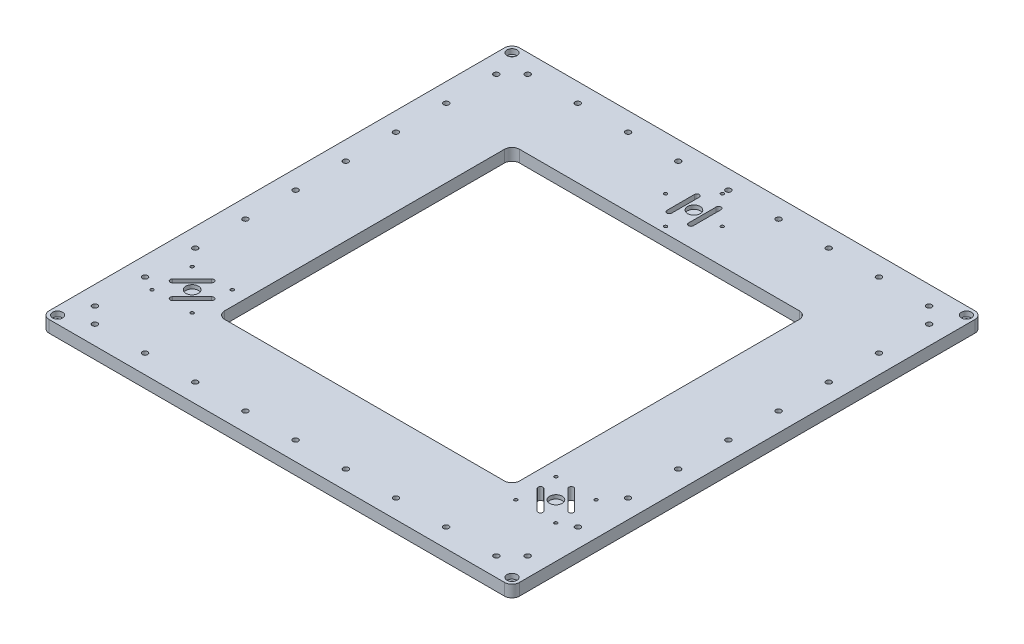
SolidWorks part; units mm, degrees
material "AISI 1045 Steel, cold drawn"
ref_plane "Front Plane" through (0, 0, 0) normal (0, 0, 1) x (1, 0, 0)
ref_plane "Top Plane" through (0, 0, 0) normal (0, 1, 0) x (1, 0, 0)
ref_plane "Right Plane" through (0, 0, 0) normal (1, 0, 0) x (0, 0, -1)
sketch "Sketch1" plane through (0, 0, 0) normal (0, 1, 0) x (1, 0, 0)
  line L1 (-187.5, -187.5) -> (187.5, -187.5)
  line L2 (-187.5, -187.5) -> (-187.5, 187.5)
  line L3 (-187.5, 187.5) -> (187.5, 187.5)
  line L4 (187.5, -187.5) -> (187.5, 187.5)
  line L5 (-187.5, -187.5) -> (187.5, 187.5) construction
  line L6 (-187.5, 187.5) -> (187.5, -187.5) construction
  point P0 (0, 0)
  dimension "D1" = 375
extrude "Boss-Extrude1" add sketch "Sketch1" along normal blind 9.525
hole_wizard "CBORE for M4 SHCS1" positions "Sketch4" profile "Sketch3" counterbore size "M4" standard "ANSI Metric" end condition up to next
sketch "Sketch4" plane through (0, 9.525, 0) normal (0, 1, 0) x (1, 0, 0)
  line L0 (0, 0) -> (-181.1218, -181.1218) construction
  line L2 (0, 0) -> (-181.1218, 0) construction
  line L3 (-181.1218, 0) -> (-181.1218, -181.1218) construction
  circle A0 centre (0, 0) radius 256.1449
  point P7 (-181.1218, -181.1218)
  dimension "D1" = 45
  dimension "D2" = 181.1218
sketch "Sketch3" plane through (-181.1218, 9.525, 181.1218) normal (1, 0, 0) x (0, 0, 1)
  line L0 (0, 0) -> (0, 9.525)
  line L1 (0, 9.525) -> (2.15, 9.525)
  line L3 (2.15, 9.525) -> (2.15, 4)
  line L4 (2.15, 4) -> (4, 4)
  line L5 (4, 4) -> (4, 0)
  line L7 (4, 0) -> (0, 0)
  line L11 (0, -6.35) -> (0, 107.95) construction
  dimension "Thru Hole Dia." = 4.3
  dimension "Thru Hole Depth" = 9.525
  dimension "C'Bore Dia." = 8
  dimension "C'Bore Depth" = 4
ref_axis "Axis1" through (0, 10.0012, 0) along (0, -1, 0)
hole_wizard "Tap Drill for M5x0.8 Tap1" positions "Sketch15" profile "Sketch16" hole size "M5x0.8" standard "ANSI Metric" end condition up to next
sketch "Sketch15" plane through (0, 9.525, 0) normal (0, 1, 0) x (1, 0, 0)
  line L1 (172.5, -172.5) -> (-172.5, -172.5)
  line L2 (172.5, -172.5) -> (172.5, 172.5)
  line L3 (172.5, 172.5) -> (-172.5, 172.5)
  line L4 (-172.5, -172.5) -> (-172.5, 172.5)
  line L5 (172.5, -172.5) -> (-172.5, 172.5) construction
  line L6 (172.5, 172.5) -> (-172.5, -172.5) construction
  line L9 (152, -152) -> (-152, -152) construction
  line L10 (152, -152) -> (152, 152) construction
  line L11 (152, 152) -> (-152, 152) construction
  line L12 (-152, -152) -> (-152, 152) construction
  line L13 (152, -152) -> (-152, 152) construction
  line L14 (152, 152) -> (-152, -152) construction
  point P1 (0, 0)
  point P86 (0, 0)
  point P191 (-160, 172.5)
  point P197 (-120, 172.5)
  point P198 (-80, 172.5)
  point P199 (-40, 172.5)
  point P200 (0, 172.5)
  point P201 (40, 172.5)
  point P202 (80, 172.5)
  point P203 (120, 172.5)
  point P204 (160, 172.5)
  point P205 (0, 0)
  dimension "D1" = 345
  dimension "D2" = 304
  dimension "D4" = 40
  dimension "D3" = 9
sketch "Sketch16" plane through (0, 9.525, 0) normal (1, 0, 0) x (0, 0, 1)
  line L0 (0, 0) -> (0, 9.525)
  line L1 (0, 9.525) -> (2.1, 9.525)
  line L2 (2.1, 9.525) -> (2.1, 0)
  line L5 (2.1, 0) -> (0, 0)
  line L11 (0, -6.35) -> (0, 107.95) construction
  dimension "Thru Hole Dia." = 4.2
  dimension "Thru Hole Depth" = 9.525
pattern_circular "CirPattern1" count 4 over 360 about axis through (0, 10.0012, 0) along (0, -1, 0) of "CBORE for M4 SHCS1", "Tap Drill for M5x0.8 Tap1"
sketch "Bed Holes" plane through (0, 9.525, 0) normal (0, 1, 0) x (1, 0, 0)
  line L0 (145, -110) -> (-145, -110) construction
  line L1 (0, -110) -> (0, 145) construction
  line L2 (152, 152) -> (152, -152) construction
  line L3 (152, 152) -> (-152, 152) construction
  line L4 (-152, 152) -> (-152, -152) construction
  line L5 (-152, -152) -> (152, -152) construction
  point P4 (0, -110)
  point P13 (0, -152)
  point P14 (152, 0)
  dimension "D1" = 255
  dimension "D2" = 7
  dimension "D3" = 304
  dimension "D4" = 7
sketch "Sketch7" plane through (0, 9.525, 0) normal (0, 1, 0) x (1, 0, 0)
  line L0 (-138.8765, -116.1235) -> (-151.1235, -103.8765) construction
  line L4 (145, -110) -> (-145, -110) construction
  line L5 (-158.9017, -111.6546) -> (-143.3454, -96.0983) construction
  line L6 (-160.2559, -110.3004) -> (-144.6996, -94.7441)
  line L7 (-157.5475, -113.0088) -> (-141.9912, -97.4525)
  line L8 (-146.6546, -123.9017) -> (-131.0983, -108.3454) construction
  line L9 (-148.0088, -122.5475) -> (-132.4525, -106.9912)
  line L10 (-145.3004, -125.2559) -> (-129.7441, -109.6996)
  line L11 (0, 0) -> (0, -187.5) construction
  line L13 (138.8765, -116.1235) -> (151.1235, -103.8765) construction
  line L14 (146.6546, -123.9017) -> (131.0983, -108.3454) construction
  line L15 (148.0088, -122.5475) -> (132.4525, -106.9912)
  line L16 (145.3004, -125.2559) -> (129.7441, -109.6996)
  line L17 (158.9017, -111.6546) -> (143.3454, -96.0983) construction
  line L18 (160.2559, -110.3004) -> (144.6996, -94.7441)
  line L19 (157.5475, -113.0088) -> (141.9912, -97.4525)
  line L20 (8.66, 145) -> (-8.66, 145) construction
  line L21 (-8.66, 156) -> (-8.66, 134) construction
  line L22 (-6.7449, 156) -> (-6.7449, 134)
  line L23 (-10.5751, 156) -> (-10.5751, 134)
  line L24 (8.66, 156) -> (8.66, 134) construction
  line L25 (10.5751, 156) -> (10.5751, 134)
  line L26 (6.7449, 156) -> (6.7449, 134)
  line L27 (-187.5, -187.5) -> (187.5, -187.5) construction
  arc A0 (-160.2559, -110.3004) -> (-157.5475, -113.0088) centre (-158.9017, -111.6546) ccw
  arc A1 (-141.9912, -97.4525) -> (-144.6996, -94.7441) centre (-143.3454, -96.0983) ccw
  arc A2 (-148.0088, -122.5475) -> (-145.3004, -125.2559) centre (-146.6546, -123.9017) ccw
  arc A3 (-129.7441, -109.6996) -> (-132.4525, -106.9912) centre (-131.0983, -108.3454) ccw
  arc A4 (148.0088, -122.5475) -> (145.3004, -125.2559) centre (146.6546, -123.9017) cw
  arc A5 (129.7441, -109.6996) -> (132.4525, -106.9912) centre (131.0983, -108.3454) cw
  arc A6 (160.2559, -110.3004) -> (157.5475, -113.0088) centre (158.9017, -111.6546) cw
  arc A7 (141.9912, -97.4525) -> (144.6996, -94.7441) centre (143.3454, -96.0983) cw
  arc A8 (-6.7449, 156) -> (-10.5751, 156) centre (-8.66, 156) ccw
  arc A9 (-10.5751, 134) -> (-6.7449, 134) centre (-8.66, 134) ccw
  arc A10 (10.5751, 156) -> (6.7449, 156) centre (8.66, 156) ccw
  arc A11 (6.7449, 134) -> (10.5751, 134) centre (8.66, 134) ccw
  point P6 (-145, -110)
  point P7 (-145, -110)
  point P9 (-151.1235, -103.8765)
  point P15 (-138.8765, -116.1235)
  point P30 (138.8765, -116.1235)
  point P37 (151.1235, -103.8765)
  point P42 (145, -110)
  point P47 (0, 145)
  point P50 (-8.66, 145)
  point P56 (8.66, 145)
  dimension "D4" = 1.9151
  dimension "D1" = 45
  dimension "D2" = 17.32
  dimension "D3" = 22
extrude "Cut-Extrude2" cut sketch "Sketch7" against normal up to surface (9.525 mm away) up to face at (-172.5, 0, 157.9)
sketch "Sketch5" plane through (0, 9.525, 0) normal (0, 1, 0) x (1, 0, 0)
  line L1 (117.5, -117.5) -> (-117.5, -117.5)
  line L2 (117.5, -117.5) -> (117.5, 117.5)
  line L3 (117.5, 117.5) -> (-117.5, 117.5)
  line L4 (-117.5, -117.5) -> (-117.5, 117.5)
  line L5 (117.5, -117.5) -> (-117.5, 117.5) construction
  line L6 (117.5, 117.5) -> (-117.5, -117.5) construction
  point P0 (0, 0)
  dimension "D1" = 235
extrude "Cut-Extrude3" cut sketch "Sketch5" against normal up to surface (9.525 mm away) up to face at (-8.66, 0, -145)
sketch "Sketch11" plane through (0, 9.525, 0) normal (0, 1, 0) x (1, 0, 0)
  line L0 (22.6274, 145) -> (0, 122.3726)
  line L1 (-129, -126) -> (-161, -126)
  line L2 (-129, -126) -> (-129, -94)
  line L3 (-129, -94) -> (-161, -94)
  line L4 (-161, -126) -> (-161, -94)
  line L5 (-129, -126) -> (-161, -94) construction
  line L6 (-129, -94) -> (-161, -126) construction
  line L7 (161, -126) -> (129, -126)
  line L8 (161, -126) -> (161, -94)
  line L9 (161, -94) -> (129, -94)
  line L10 (129, -126) -> (129, -94)
  line L11 (161, -126) -> (129, -94) construction
  line L12 (161, -94) -> (129, -126) construction
  line L13 (22.6274, 145) -> (0, 167.6274)
  line L14 (0, 122.3726) -> (-22.6274, 145)
  line L15 (0, 167.6274) -> (-22.6274, 145)
  line L16 (22.6274, 145) -> (-22.6274, 145) construction
  line L17 (0, 122.3726) -> (0, 167.6274) construction
  line L18 (0, -110) -> (0, 145) construction
  point P0 (-145, -110)
  point P6 (145, -110)
  point P13 (0, 145)
  dimension "D1" = 32
hole_wizard "Tap Drill for M3x0.5 Tap2" positions "Sketch12" profile "Sketch13" hole size "M3x0.5" standard "ANSI Metric" end condition up to next
sketch "Sketch12" plane through (0, 9.525, 0) normal (0, 1, 0) x (1, 0, 0)
  point P0 (-161, -126)
  point P3 (-129, -94)
  point P6 (129, -94)
  point P9 (161, -126)
  point P12 (0, 122.3726)
  point P15 (0, 167.6274)
  point P19 (-161, -94)
  point P22 (-129, -126)
  point P25 (129, -126)
  point P28 (161, -94)
  point P31 (22.6274, 145)
  point P34 (-22.6274, 145)
sketch "Sketch13" plane through (-161, 9.525, 126) normal (1, 0, 0) x (0, 0, 1)
  line L0 (0, 0) -> (0, 9.525)
  line L1 (0, 9.525) -> (1.25, 9.525)
  line L2 (1.25, 9.525) -> (1.25, 0)
  line L5 (1.25, 0) -> (0, 0)
  line L11 (0, -6.35) -> (0, 107.95) construction
  dimension "Thru Hole Dia." = 2.5
  dimension "Thru Hole Depth" = 9.525
sketch "Sketch14" plane through (0, 9.525, 0) normal (0, 1, 0) x (1, 0, 0)
  circle A0 centre (0, 145) radius 5
  circle A1 centre (145, -110) radius 5
  circle A2 centre (-145, -110) radius 5
  dimension "D1" = 10
extrude "Cut-Extrude4" cut sketch "Sketch14" against normal blind 3
fillet "Fillet2" radius 6 8 edges at (-117.5, 4.7625, 117.5) (117.5, 4.7625, -117.5) (117.5, 4.7625, 117.5) (-117.5, 4.7625, -117.5) (187.5, 4.7625, 187.5) (-187.5, 4.7625, 187.5) (187.5, 4.7625, -187.5) (-187.5, 4.7625, -187.5)
